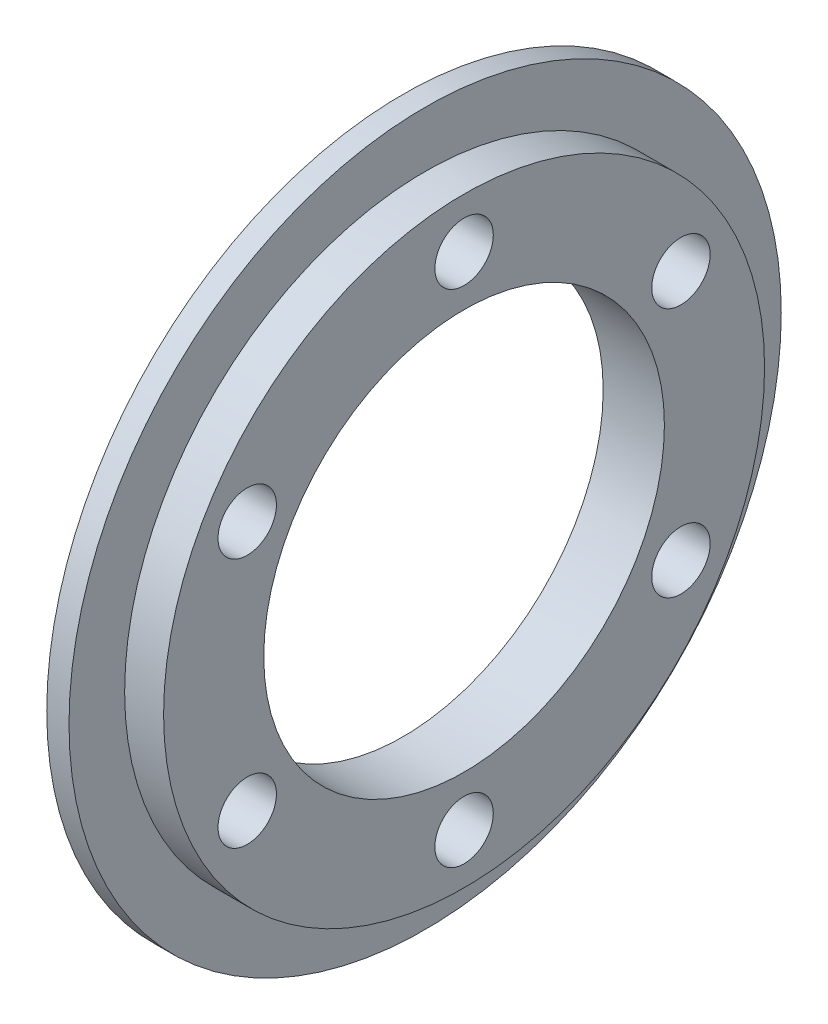
SolidWorks part; units mm, degrees
material "AISI 4130 Steel, annealed at 865C"
ref_plane "Front Plane" through (0, 0, 0) normal (0, 0, 1) x (1, 0, 0)
ref_plane "Top Plane" through (0, 0, 0) normal (0, 1, 0) x (1, 0, 0)
ref_plane "Right Plane" through (0, 0, 0) normal (1, 0, 0) x (0, 0, -1)
sketch "Sketch1" plane through (0, 0, 0) normal (0, 1, 0) x (1, 0, 0)
  line L0 (0, 67.825) -> (0, 47)
  line L1 (0, -47) -> (0, -53)
  line L2 (0, -63) -> (0, -67.825)
  line L3 (-1, -36) -> (0, 36) construction
  line L4 (-0.5, 0) -> (17, 0) construction
  line L5 (0, 54) -> (0, 36)
  line L6 (17, 36) -> (-1, 36)
  line L7 (-1, -36) -> (17, -36)
  line L8 (-1, -36) -> (17, -36) construction
  line L9 (11, 36) -> (0, 36)
  line L10 (11, 36) -> (11, 54)
  line L11 (11, 54) -> (4, 54)
  line L12 (11, 45) -> (0, 45) construction
  line L15 (0, 54) -> (0, 64)
  line L16 (0, 64) -> (4, 64)
  line L17 (4, 54) -> (4, 64)
  dimension "D1" = 45
  dimension "D2" = 18
  dimension "D3" = 11
  dimension "D4" = 4
  dimension "D5" = 10
revolve "Revolve1" add sketch "Sketch1" angle 360 about L4
hole_wizard "M10 Clearance Hole1" positions "Sketch2" profile "Sketch3" hole size "M10" standard "ANSI Metric" end condition through all
sketch "Sketch2" plane through (11, 0, 0) normal (1, 0, 0) x (0, 0, -1)
  line L0 (0, 0) -> (0, 45) construction
  circle A1 centre (0, 0) radius 45 construction
  point P64 (0, 45)
  point P69 (38.9711, 22.5)
  point P70 (38.9711, -22.5)
  point P71 (0, -45)
  point P72 (-38.9711, -22.5)
  point P73 (-38.9711, 22.5)
  dimension "D1" = 90
  dimension "D3" = 45
  dimension "D2" = 6
sketch "Sketch3" plane through (11, 22.5, 38.9711) normal (0, 1, 0) x (0, 0, -1)
  line L0 (0, 0) -> (0, 11)
  line L1 (0, 11) -> (5.25, 11)
  line L2 (5.25, 11) -> (5.25, 0)
  line L5 (5.25, 0) -> (0, 0)
  line L11 (0, -6.35) -> (0, 107.95) construction
  dimension "Thru Hole Dia." = 10.5
  dimension "Thru Hole Depth" = 11
